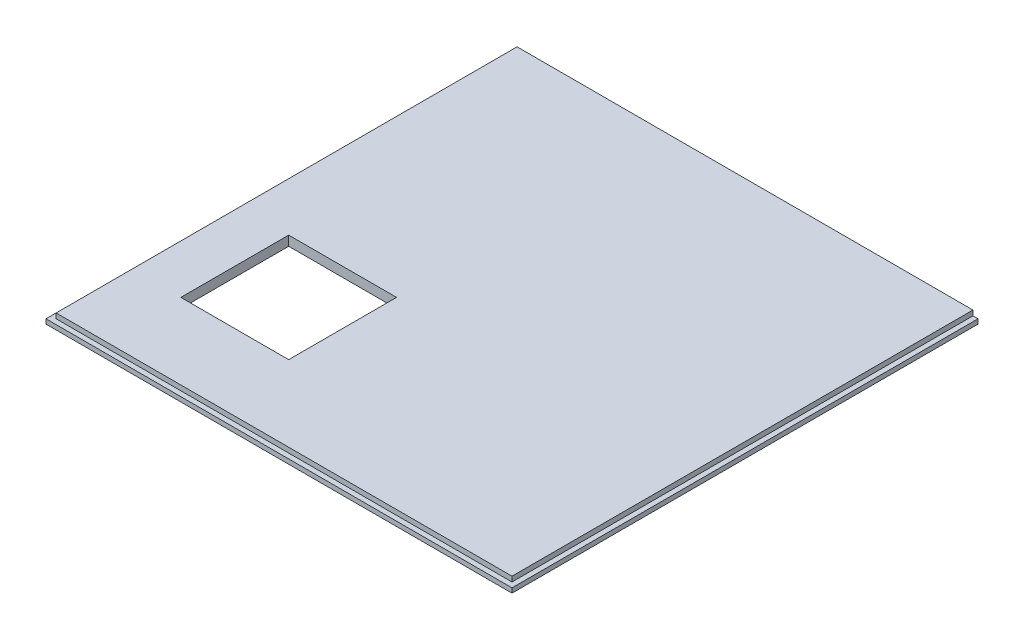
SolidWorks part; units mm, degrees
ref_plane "Front Plane" through (0, 0, 0) normal (0, 0, 1) x (1, 0, 0)
ref_plane "Top Plane" through (0, 0, 0) normal (0, 1, 0) x (1, 0, 0)
ref_plane "Right Plane" through (0, 0, 0) normal (1, 0, 0) x (0, 0, -1)
sketch "Sketch1" plane through (0, 0, 0) normal (0, 1, 0) x (1, 0, 0)
  line L0 (-235.7438, -184.9437) -> (-235.7437, -438.9437) construction
  line L1 (-438.9437, -438.9437) -> (438.9438, -438.9437)
  line L2 (-438.9437, -438.9437) -> (-438.9437, 438.9438)
  line L3 (-438.9437, 438.9438) -> (438.9438, 438.9438)
  line L4 (438.9438, -438.9437) -> (438.9438, 438.9438)
  line L5 (-438.9437, -438.9437) -> (438.9438, 438.9438) construction
  line L6 (-438.9437, 438.9438) -> (438.9438, -438.9437) construction
  line L7 (-337.3438, -83.3437) -> (-134.1438, -83.3437)
  line L8 (-337.3438, -83.3437) -> (-337.3438, -286.5437)
  line L9 (-337.3438, -286.5437) -> (-134.1438, -286.5437)
  line L10 (-134.1438, -83.3437) -> (-134.1438, -286.5437)
  line L11 (-337.3438, -83.3437) -> (-134.1438, -286.5437) construction
  line L12 (-337.3438, -286.5437) -> (-134.1438, -83.3437) construction
  line L13 (-235.7438, -184.9437) -> (-438.9437, -184.9437) construction
  point P0 (0, 0)
  point P6 (-235.7438, -184.9437)
  point P13 (0, 0)
  point P15 (0, 0)
  point P16 (0, 0)
  point P17 (-134.1438, -86.2458)
  point P18 (-134.1438, -85.2254)
  dimension "D1" = 877.8875
  dimension "D2" = 877.8875
  dimension "D3" = 254
  dimension "D4" = 203.2
extrude "Boss-Extrude1" add sketch "Sketch1" along normal blind 18.2562 contours L1 L4 L3 L2 L7 L10 L9 L8 region at (13.3452, 0, -10.4694)
sketch "Sketch3" plane through (0, 18.2562, 0) normal (0, 1, 0) x (1, 0, 0)
  line L3 (429.4188, 438.9438) -> (438.9437, 438.9437)
  line L5 (438.9437, 438.9437) -> (438.9437, -438.9437)
  line L6 (429.4188, -429.4187) -> (429.4188, 438.9438)
  line L7 (-429.4187, -429.4187) -> (429.4188, -429.4187)
  line L8 (-429.4187, 438.9438) -> (-429.4187, -429.4187)
  line L9 (429.4188, -429.4187) -> (429.4188, 438.9438)
  line L10 (-429.4187, -429.4187) -> (429.4188, -429.4187)
  line L11 (-429.4187, 438.9438) -> (-429.4187, -429.4187)
  line L12 (438.9437, -438.9437) -> (-438.9437, -438.9437)
  line L13 (-438.9437, 438.9437) -> (-438.9437, -438.9437)
  line L14 (438.9437, 438.9437) -> (-438.9437, -438.9437) construction
  line L15 (438.9437, -438.9437) -> (-438.9437, 438.9437) construction
  line L16 (-429.4187, 438.9438) -> (-438.9437, 438.9437)
  point P0 (0, 0)
  dimension "D1" = 9.525
extrude "Cut-Extrude1" cut sketch "Sketch3" against normal blind 9.525
